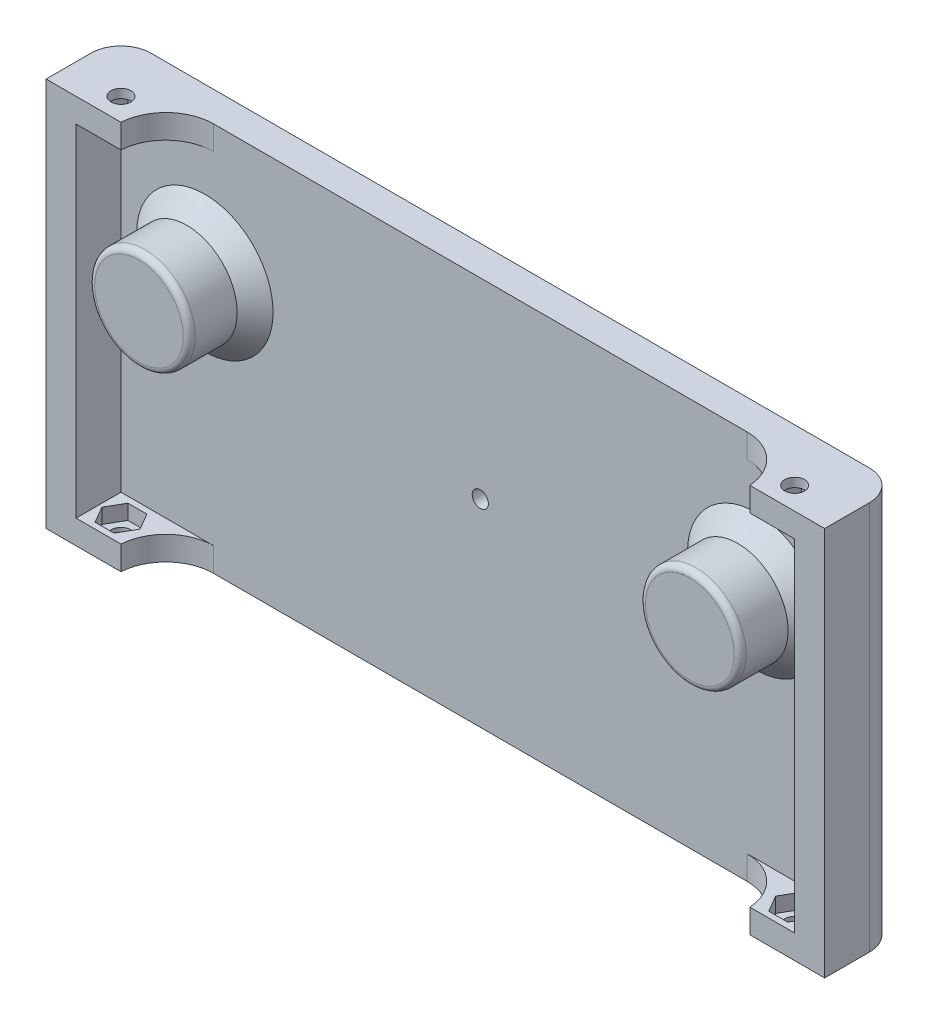
SolidWorks part; units mm, degrees
ref_plane "Front Plane" through (0, 0, 0) normal (0, 0, 1) x (1, 0, 0)
ref_plane "Top Plane" through (0, 0, 0) normal (0, 1, 0) x (1, 0, 0)
ref_plane "Right Plane" through (0, 0, 0) normal (1, 0, 0) x (0, 0, -1)
sketch "Sketch1" plane through (0, 0, 0) normal (0, 0, 1) x (1, 0, 0)
  line L1 (0, 0) -> (130, 0)
  line L2 (0, 0) -> (0, 65)
  line L3 (0, 65) -> (130, 65)
  line L4 (130, 0) -> (130, 65)
  dimension "D1" = 65
  dimension "D2" = 130
extrude "Boss-Extrude1" add sketch "Sketch1" along normal blind 12.5
sketch "Sketch3" plane through (0, 65, 0) normal (0, 1, 0) x (1, 0, 0)
  line L0 (5, -12.5) -> (125, -12.5)
  line L9 (125, -5) -> (125, -12.5)
  line L10 (5, -5) -> (125, -5)
  line L11 (5, -12.5) -> (5, -5)
  line L12 (125, -5) -> (125, -12.5)
  line L13 (5, -5) -> (125, -5)
  line L14 (5, -12.5) -> (5, -5)
  dimension "D1" = 5
extrude "Cut-Extrude1" cut sketch "Sketch3" against normal through all
fillet "Fillet1" radius 5 2 edges at (130, 32.5, 0) (0, 32.5, 0)
sketch "Sketch4" plane through (0, 0, 0) normal (0, -1, 0) x (1, 0, 0)
  line L0 (125, 5) -> (5, 5) construction
  line L1 (5, 12.5) -> (12.5, 12.5)
  line L2 (5, 12.5) -> (5, 5)
  line L3 (5, 5) -> (12.5, 5)
  line L4 (12.5, 12.5) -> (12.5, 5)
  line L6 (125, 5) -> (117.5, 5)
  line L7 (125, 5) -> (125, 12.5)
  line L8 (125, 12.5) -> (117.5, 12.5)
  line L9 (117.5, 5) -> (117.5, 12.5)
extrude "Boss-Extrude2" add sketch "Sketch4" against normal blind 4
sketch "Sketch5" plane through (0, 4, 0) normal (0, 1, 0) x (1, 0, 0)
  line L0 (121.25, -5) -> (121.25, -12.5) construction
  line L1 (117.5, -5) -> (125, -5) construction
  line L2 (125, -12.5) -> (117.5, -12.5) construction
  line L3 (65, 0) -> (65, -12.5) construction
  line L4 (124.4254, -8.75) -> (122.8377, -6)
  line L5 (122.8377, -6) -> (119.6623, -6)
  line L6 (119.6623, -6) -> (118.0746, -8.75)
  line L7 (118.0746, -8.75) -> (119.6623, -11.5)
  line L8 (119.6623, -11.5) -> (122.8377, -11.5)
  line L9 (122.8377, -11.5) -> (124.4254, -8.75)
  line L10 (125, 0) -> (5, 0) construction
  line L11 (10.3377, -6) -> (11.9254, -8.75)
  line L12 (11.9254, -8.75) -> (10.3377, -11.5)
  line L13 (7.1623, -11.5) -> (5.5746, -8.75)
  line L14 (10.3377, -11.5) -> (7.1623, -11.5)
  line L15 (7.1623, -6) -> (10.3377, -6)
  line L16 (5.5746, -8.75) -> (7.1623, -6)
  circle A0 centre (121.25, -8.75) radius 2.75 construction
  circle A1 centre (121.25, -8.75) radius 1.65
  circle A2 centre (8.75, -8.75) radius 1.65
  dimension "D2" = 3.3
  dimension "D1" = 5.5
extrude "Cut-Extrude2" cut sketch "Sketch5" against normal blind 2.5
extrude "Cut-Extrude3" cut sketch "Sketch5<3>" against normal through all contours A2 | A1 region at (121.25, 4, 8.75) region at (8.75, 4, 8.75)
sketch "Sketch5<3>" plane through (0, 4, 0) normal (0, 1, 0) x (1, 0, 0) same geometry as "Sketch5"
fillet "Fillet2" radius 8 2 edges at (117.5, 2, 5) (12.5, 2, 5)
ref_plane "Plane1" through (0, 32.5, 0) normal (0, 1, 0) x (1, 0, 0)
mirror "Mirror1" about plane through (0, 32.5, 0) normal (0, 1, 0) of "Cut-Extrude3", "Cut-Extrude2", "Boss-Extrude2", "Fillet2"
sketch "Sketch7" plane through (0, 0, 5) normal (0, 0, 1) x (1, 0, 0)
  line L0 (130, 0) -> (111, 0) construction
  line L1 (109.5156, 0) -> (20.4844, 0) construction
  line L2 (111, 0) -> (111, 42.7) construction
  line L3 (65, 65) -> (65, 0) construction
  line L4 (109.5156, 65) -> (20.4844, 65) construction
  circle A0 centre (111, 42.7) radius 8.4
  circle A1 centre (19, 42.7) radius 8.4
  dimension "D3" = 16.8
  dimension "D1" = 19
  dimension "D2" = 42.7
extrude "Boss-Extrude3" add sketch "Sketch7" along normal blind 11
fillet "Fillet3" radius 1 2 edges at (119.4, 42.7, 16) (10.6, 42.7, 16)
chamfer "Chamfer1" distance 3 angle 45 2 edges at (102.6, 42.7, 5) (10.6, 42.7, 5)
sketch "Sketch8" plane through (0, 0, 0) normal (0, 0, -1) x (-1, 0, 0)
  line L0 (-65, 65) -> (-65, 33) construction
  line L1 (-125, 65) -> (-5, 65) construction
  circle A0 centre (-65, 33) radius 1.35
  dimension "D2" = 2.7
  dimension "D1" = 32
extrude "Cut-Extrude4" cut sketch "Sketch8" against normal through all
